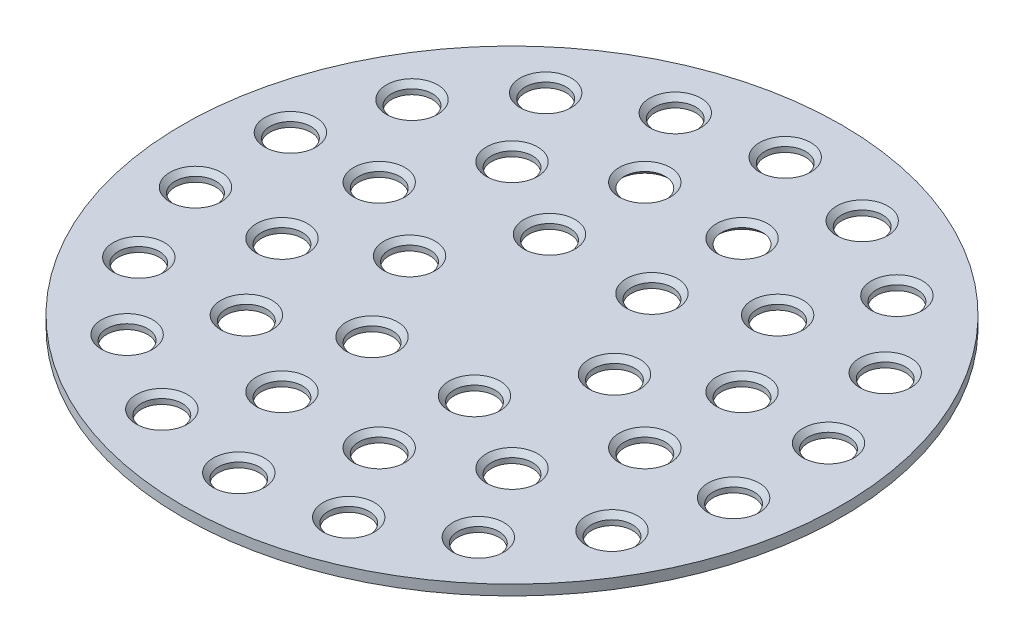
SolidWorks part; units mm, degrees
ref_plane "Front Plane" through (0, 0, 0) normal (0, 0, 1) x (1, 0, 0)
ref_plane "Top Plane" through (0, 0, 0) normal (0, 1, 0) x (1, 0, 0)
ref_plane "Right Plane" through (0, 0, 0) normal (1, 0, 0) x (0, 0, -1)
sketch "Sketch1" plane through (0, 0, 0) normal (0, 1, 0) x (1, 0, 0)
  circle A0 centre (0, 0) radius 96.5
  dimension "D1" = 193
extrude "Boss-Extrude1" add sketch "Sketch1" along normal blind 3
sketch "Sketch2" plane through (0, 3, 0) normal (0, 1, 0) x (1, 0, 0)
  line L0 (0, 0) -> (53.1259, 14.235) construction
  line L1 (0, 0) -> (78.7846, 13.8919) construction
  line L2 (0, 0) -> (67.4302, 0) construction
  circle A0 centre (30, 0) radius 6
  circle A1 centre (53.1259, 14.235) radius 6
  circle A2 centre (78.7846, 13.8919) radius 6
  circle A3 centre (15, -25.9808) radius 6
  circle A4 centre (-15, -25.9808) radius 6
  circle A5 centre (-30, 0) radius 6
  circle A6 centre (-15, 25.9808) radius 6
  circle A7 centre (15, 25.9808) radius 6
  circle A8 centre (53.1259, -14.235) radius 6
  circle A9 centre (38.8909, -38.8909) radius 6
  circle A10 centre (14.235, -53.1259) radius 6
  circle A11 centre (-14.235, -53.1259) radius 6
  circle A12 centre (-38.8909, -38.8909) radius 6
  circle A13 centre (-53.1259, -14.235) radius 6
  circle A14 centre (-53.1259, 14.235) radius 6
  circle A15 centre (-38.8909, 38.8909) radius 6
  circle A16 centre (-14.235, 53.1259) radius 6
  circle A17 centre (14.235, 53.1259) radius 6
  circle A18 centre (38.8909, 38.8909) radius 6
  circle A19 centre (78.7846, -13.8919) radius 6
  circle A20 centre (69.282, -40) radius 6
  circle A21 centre (51.423, -61.2836) radius 6
  circle A22 centre (27.3616, -75.1754) radius 6
  circle A23 centre (0, -80) radius 6
  circle A24 centre (-27.3616, -75.1754) radius 6
  circle A25 centre (-51.423, -61.2836) radius 6
  circle A26 centre (-69.282, -40) radius 6
  circle A27 centre (-78.7846, -13.8919) radius 6
  circle A28 centre (-78.7846, 13.8919) radius 6
  circle A29 centre (-69.282, 40) radius 6
  circle A30 centre (-51.423, 61.2836) radius 6
  circle A31 centre (-27.3616, 75.1754) radius 6
  circle A32 centre (0, 80) radius 6
  circle A33 centre (27.3616, 75.1754) radius 6
  circle A34 centre (51.423, 61.2836) radius 6
  circle A35 centre (69.282, 40) radius 6
  point P18 (0, 0)
  point P41 (0, 0)
  point P76 (0, 0)
  dimension "D2" = 12
  dimension "D3" = 12
  dimension "D4" = 12
  dimension "D1" = 6
  dimension "D7" = 55
  dimension "D8" = 80
  dimension "D9" = 15
  dimension "D10" = 10
  dimension "D5" = 12
  dimension "D6" = 18
extrude "Cut-Extrude3" cut sketch "Sketch2" against normal blind 10
chamfer "Chamfer3" distance 1.5 angle 45 38 edges at (14.235, 0, -47.1259) (14.235, 3, -47.1259) (-14.235, 0, -47.1259) (-14.235, 3, -47.1259) (27.3616, 3, -69.1754) (-38.8909, 3, -32.8909) (-69.282, 3, -34) (-51.423, 3, -55.2836) (-27.3616, 3, -69.1754) (0, 3, -74) (78.7846, 3, 19.8919) (78.7846, 3, -7.8919) (53.1259, 3, -8.235) (30, 3, 6) (53.1259, 3, 20.235) (69.282, 3, 46) (51.423, 3, 67.2836) (27.3616, 3, 81.1754) (38.8909, 3, 44.8909) (15, 3, 31.9808) (14.235, 3, 59.1259) (0, 3, 86) (-27.3616, 3, 81.1754) (-14.235, 3, 59.1259) (-51.423, 3, 67.2836) (-15, 3, 31.9808) (-38.8909, 3, 44.8909) (-69.282, 3, 46) (-53.1259, 3, 20.235) (-30, 3, 6) (-78.7846, 3, 19.8919) (-78.7846, 3, -7.8919) (-53.1259, 3, -8.235) (-15, 3, -19.9808) (15, 3, -19.9808) (38.8909, 3, -32.8909) (69.282, 3, -34) (51.423, 3, -55.2836)
